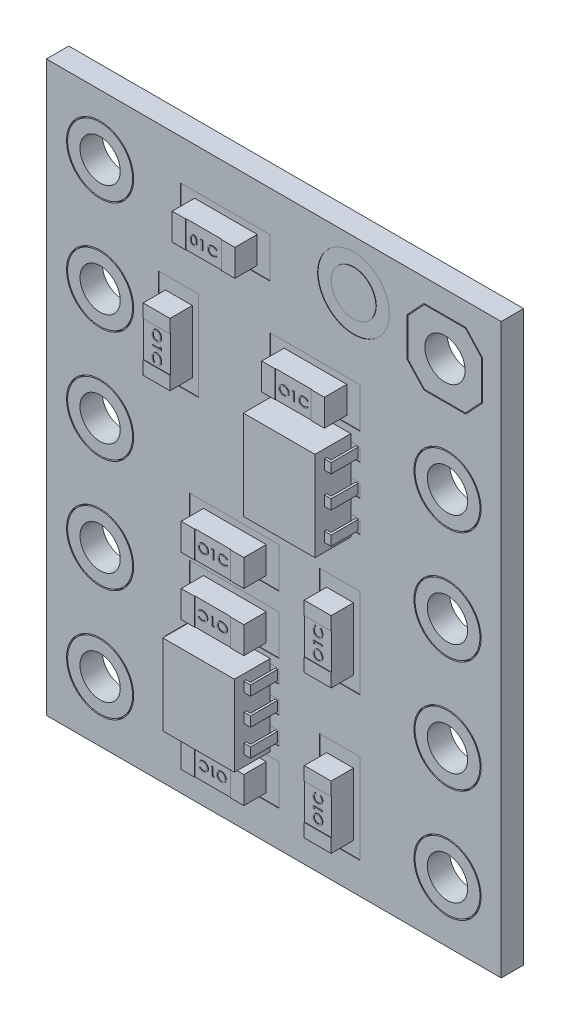
SolidWorks part; units mm, degrees
ref_plane "Alzado" through (0, 0, 0) normal (0, 0, 1) x (1, 0, 0)
ref_plane "Planta" through (0, 0, 0) normal (0, 1, 0) x (1, 0, 0)
ref_plane "Vista lateral" through (0, 0, 0) normal (1, 0, 0) x (0, 0, -1)
sketch "Croquis1" plane through (0, 0, 0) normal (0, 0, 1) x (1, 0, 0)
  line L0 (0, -0.275) -> (0, 0.275) construction
  line L1 (-5.08, 6.35) -> (5.08, 6.35)
  line L2 (-5.08, 6.35) -> (-5.08, -6.35)
  line L3 (-5.08, -6.35) -> (5.08, -6.35)
  line L4 (5.08, 6.35) -> (5.08, -6.35)
  line L6 (0.275, 0) -> (-0.275, 0) construction
  point P4 (-5.08, 0)
  point P5 (0, 6.35)
  dimension "D1" = 10.16
  dimension "D2" = 12.7
extrude "Saliente-Extruir2" add sketch "Croquis1" along normal blind 0.5
sketch "Croquis2" plane through (0, 0, 0.5) normal (0, 0, 1) x (1, 0, 0)
  line L0 (-3.88, 6.35) -> (-3.88, -6.35) construction
  line L1 (5.08, 6.35) -> (-5.08, 6.35) construction
  line L2 (-5.08, -6.35) -> (5.08, -6.35) construction
  line L3 (-5.08, 6.35) -> (-5.08, -6.35) construction
  line L4 (3.88, 6.35) -> (3.88, -6.35) construction
  line L5 (5.08, -6.35) -> (5.08, 6.35) construction
  line L6 (2.9786, 5.433) -> (2.9786, 4.567)
  line L7 (3.0025, 5.4294) -> (3.0025, 4.5706)
  line L8 (3.88, 5.8391) -> (3.355, 5.8391)
  line L9 (4.6663, 4.5655) -> (4.6663, 5.4331)
  line L10 (3.0025, 4.5706) -> (3.3638, 4.1809)
  line L11 (3.355, 4.1609) -> (4.2913, 4.1609)
  line L12 (3.88, 5.8191) -> (3.3638, 5.8191)
  line L13 (2.9786, 4.567) -> (3.355, 4.1609)
  line L14 (2.9786, 5.433) -> (3.355, 5.8391)
  line L15 (4.6663, 4.5655) -> (4.2913, 4.1609)
  line L16 (3.0019, 5.1573) -> (2.9033, 4.9865) [skipped]
  line L17 (4.2913, 4.1609) -> (4.2913, 5.9445) construction
  line L18 (3.3638, 4.1809) -> (3.88, 4.1809)
  line L19 (4.8787, 4.9484) -> (4.7801, 5.1192) [skipped]
  line L20 (4.3347, 4.1093) -> (4.5847, 4.5424) [skipped]
  line L21 (3.1533, 4.5805) -> (3.4033, 4.1474) [skipped]
  line L22 (4.6663, 5.4331) -> (4.2913, 5.8391)
  line L23 (3.88, 4.1809) -> (4.2826, 4.1809)
  line L24 (4.2913, 5.8391) -> (3.88, 5.8391)
  line L25 (3.88, 5.8191) -> (4.2825, 5.8191)
  line L26 (3.0025, 5.4294) -> (3.3638, 5.8191)
  line L27 (4.2825, 5.8191) -> (4.6425, 5.4294)
  line L28 (4.6425, 4.5693) -> (4.2826, 4.1809)
  line L29 (4.6425, 5.4294) -> (4.6425, 4.5693)
  line L31 (3.416, 5.7883) -> (3.3781, 5.7228) [skipped]
  line L32 (4.8041, 5.0837) -> (4.7663, 5.1492) [skipped]
  line L33 (4.4279, 4.2646) -> (4.4657, 4.3301) [skipped]
  line L34 (2.9653, 4.9923) -> (3.0031, 4.9268) [skipped]
  circle A0 centre (-3.88, 5) radius 0.75
  circle A1 centre (-3.88, 2.5) radius 0.75
  circle A2 centre (-3.88, 0) radius 0.75
  circle A3 centre (-3.88, -2.5) radius 0.75
  circle A4 centre (-3.88, -5) radius 0.75
  circle A5 centre (-3.88, 5) radius 0.725
  circle A6 centre (3.88, 2.5) radius 0.75
  circle A7 centre (3.88, 0) radius 0.75
  circle A8 centre (3.88, -2.5) radius 0.75
  circle A9 centre (3.88, -5) radius 0.75
  circle A10 centre (-3.88, 2.5) radius 0.725
  circle A11 centre (-3.88, 0) radius 0.725
  circle A12 centre (-3.88, -2.5) radius 0.725
  circle A13 centre (-3.88, -5) radius 0.725
  circle A14 centre (3.88, -5) radius 0.725
  circle A15 centre (3.88, -2.5) radius 0.725
  circle A16 centre (3.88, 0) radius 0.725
  circle A17 centre (3.88, 2.5) radius 0.725
  dimension "D2" = 1.5
  dimension "D3" = 1.5
  dimension "D4" = 1.5
  dimension "D5" = 1.5
  dimension "D6" = 1.5
  dimension "D13" = 1.45
  dimension "D14" = 1.5
  dimension "D15" = 1.5
  dimension "D16" = 1.5
  dimension "D17" = 1.5
  dimension "D20" = 1.45
  dimension "D21" = 1.45
  dimension "D22" = 1.45
  dimension "D23" = 1.45
  dimension "D24" = 1.45
  dimension "D25" = 1.45
  dimension "D26" = 1.45
  dimension "D27" = 1.45
  dimension "D1" = 1.2
  dimension "D7" = 1.35
  dimension "D8" = 2.5
  dimension "D9" = 2.5
  dimension "D10" = 2.5
  dimension "D11" = 2.5
  dimension "D12" = 1.2
  dimension "D18" = 2.5
  dimension "D19" = 2.5
  dimension "D28" = 0.02
  dimension "D29" = 0.02
  dimension "D30" = 0.02
  dimension "D31" = 0.02
  dimension "D32" = 0.02
  dimension "D35" = 0.02
extrude "Cortar-Extruir1" cut sketch "Croquis2" against normal blind 0.05
sketch "Croquis3" plane through (0, 0, 0.5) normal (0, 0, 1) x (1, 0, 0)
  line L0 (3.8231, 5.8191) -> (3.8232, 4.1809) construction
  line L1 (4.2825, 5.8191) -> (3.3638, 5.8191) construction
  line L2 (3.3638, 4.1809) -> (4.2826, 4.1809) construction
  line L3 (3.0025, 5) -> (4.6425, 4.9993) construction
  line L4 (3.0025, 5.4294) -> (3.0025, 4.5706) construction
  line L5 (4.6425, 4.5693) -> (4.6425, 5.4294) construction
  circle A0 centre (-3.88, -5) radius 0.45
  circle A1 centre (-3.88, -2.5) radius 0.45
  circle A2 centre (-3.88, 0) radius 0.45
  circle A3 centre (-3.88, 2.5) radius 0.45
  circle A4 centre (-3.88, 5) radius 0.45
  circle A5 centre (3.88, 2.5) radius 0.45
  circle A6 centre (3.88, 0) radius 0.45
  circle A7 centre (3.88, -2.5) radius 0.45
  circle A8 centre (3.88, -5) radius 0.45
  circle A9 centre (3.8232, 5) radius 0.45
  dimension "D1" = 0.9
  dimension "D2" = 0.9
  dimension "D3" = 0.9
  dimension "D4" = 0.9
  dimension "D5" = 0.9
  dimension "D6" = 0.9
  dimension "D7" = 0.9
  dimension "D8" = 0.9
  dimension "D9" = 0.9
  dimension "D10" = 0.9
extrude "Cortar-Extruir2" cut sketch "Croquis3" against normal blind 30.05
sketch "Croquis4" plane through (0, 0, 0.5) normal (0, 0, 1) x (1, 0, 0)
  line L0 (5.08, 6.35) -> (-5.08, 6.35) construction
  line L1 (5.08, -6.35) -> (5.08, 6.35) construction
  circle A0 centre (1.78, 5.25) radius 0.5
  circle A1 centre (1.78, 5.25) radius 0.8
  dimension "D3" = 1.6
  dimension "D4" = 1
  dimension "D1" = 1.1
  dimension "D2" = 3.3
extrude "Cortar-Extruir3" cut sketch "Croquis4" against normal blind 0.01
sketch "Croquis5" plane through (0, 0, 0.5) normal (0, 0, 1) x (1, 0, 0)
  line L0 (-5.08, 6.35) -> (-5.08, -6.35) construction
  line L1 (-2.08, 5.45) -> (-0.08, 5.45)
  line L2 (-2.08, 5.45) -> (-2.08, 4.55)
  line L3 (-2.08, 4.55) -> (-0.08, 4.55)
  line L4 (-0.08, 5.45) -> (-0.08, 4.55)
  line L5 (5.08, 6.35) -> (-5.08, 6.35) construction
  line L6 (-0.08, 2.05) -> (0.22, 2.05)
  line L7 (1.92, 3.55) -> (-0.08, 3.55)
  line L8 (1.92, 3.55) -> (1.92, 2.65)
  line L9 (1.92, 2.65) -> (-0.08, 2.65)
  line L10 (-0.08, 3.55) -> (-0.08, 2.65)
  line L11 (-2.58, 3.5) -> (-1.68, 3.5)
  line L12 (-2.58, 3.5) -> (-2.58, 1.5)
  line L13 (-2.58, 1.5) -> (-1.68, 1.5)
  line L14 (-1.68, 3.5) -> (-1.68, 1.5)
  line L15 (-0.08, 2.35) -> (0.22, 2.35)
  line L16 (-0.08, 2.35) -> (-0.08, 2.05)
  line L17 (-0.08, 0.65) -> (0.22, 0.65)
  line L18 (0.22, 2.35) -> (0.22, 2.05)
  line L19 (1.92, 2.35) -> (1.62, 2.35)
  line L20 (1.92, 2.35) -> (1.92, 2.05)
  line L21 (1.92, 0.65) -> (1.62, 0.65)
  line L22 (1.62, 2.35) -> (1.62, 2.05)
  line L23 (1.92, 0.95) -> (1.92, 0.65)
  line L24 (1.92, 1.65) -> (1.62, 1.65)
  line L25 (-0.08, 1.65) -> (-0.08, 1.35)
  line L26 (-0.08, 1.35) -> (0.22, 1.35)
  line L27 (-1.88, -3.15) -> (-1.58, -3.15)
  line L28 (1.92, 0.95) -> (1.62, 0.95)
  line L29 (-0.08, 0.95) -> (-0.08, 0.65)
  line L30 (0.22, 0.95) -> (0.22, 0.65)
  line L32 (0.22, 1.65) -> (0.22, 1.35)
  line L33 (1.62, 1.65) -> (1.62, 1.35)
  line L34 (1.92, 1.65) -> (1.92, 1.35)
  line L35 (1.62, 0.95) -> (1.62, 0.65)
  line L36 (1.62, 1.35) -> (1.92, 1.35)
  line L37 (0.22, 1.65) -> (-0.08, 1.65)
  line L38 (1.62, 2.05) -> (1.92, 2.05)
  line L39 (0.22, 0.95) -> (-0.08, 0.95)
  line L40 (-1.88, -3.45) -> (-1.88, -3.75)
  line L41 (-1.88, -0.45) -> (0.12, -0.45)
  line L42 (-1.88, -0.45) -> (-1.88, -1.35)
  line L43 (-1.88, -1.35) -> (0.12, -1.35)
  line L44 (0.12, -0.45) -> (0.12, -1.35)
  line L45 (-1.88, -1.75) -> (0.12, -1.75)
  line L46 (-1.88, -1.75) -> (-1.88, -2.65)
  line L47 (-1.88, -2.65) -> (0.12, -2.65)
  line L48 (0.12, -1.75) -> (0.12, -2.65)
  line L49 (-1.88, -4.65) -> (0.12, -4.65)
  line L50 (-1.88, -4.65) -> (-1.88, -5.55)
  line L51 (-1.88, -5.55) -> (0.12, -5.55)
  line L52 (0.12, -4.65) -> (0.12, -5.55)
  line L53 (-1.88, -2.85) -> (-1.58, -2.85)
  line L54 (-1.88, -2.85) -> (-1.88, -3.15)
  line L55 (-1.88, -4.35) -> (-1.58, -4.35)
  line L56 (-1.58, -2.85) -> (-1.58, -3.15)
  line L57 (0.12, -2.85) -> (-0.18, -2.85)
  line L58 (0.12, -2.85) -> (0.12, -3.15)
  line L59 (0.12, -4.35) -> (-0.18, -4.35)
  line L60 (-0.18, -2.85) -> (-0.18, -3.15)
  line L61 (-1.88, -3.75) -> (-1.58, -3.75)
  line L62 (0.12, -3.45) -> (-0.18, -3.45)
  line L64 (-1.88, -4.05) -> (-1.58, -4.05)
  line L65 (-1.88, -4.05) -> (-1.88, -4.35)
  line L66 (-1.58, -3.45) -> (-1.58, -3.75)
  line L67 (-0.18, -3.15) -> (0.12, -3.15)
  line L68 (-1.58, -3.45) -> (-1.88, -3.45)
  line L69 (-0.18, -3.45) -> (-0.18, -3.75)
  line L70 (0.12, -3.45) -> (0.12, -3.75)
  line L72 (-1.58, -4.05) -> (-1.58, -4.35)
  line L73 (-0.18, -3.75) -> (0.12, -3.75)
  line L74 (-0.18, -4.05) -> (0.12, -4.05)
  line L75 (-0.18, -4.05) -> (-0.18, -4.35)
  line L76 (0.12, -4.05) -> (0.12, -4.35)
  line L77 (1.92, -0.45) -> (1.02, -0.45)
  line L78 (1.92, -0.45) -> (1.92, -2.45)
  line L79 (1.92, -2.45) -> (1.02, -2.45)
  line L80 (1.02, -0.45) -> (1.02, -2.45)
  line L81 (1.02, -3.65) -> (1.92, -3.65)
  line L82 (1.02, -3.65) -> (1.02, -5.65)
  line L83 (1.02, -5.65) -> (1.92, -5.65)
  line L84 (1.92, -3.65) -> (1.92, -5.65)
  dimension "D1" = 0.9
  dimension "D2" = 2
  dimension "D3" = 3
  dimension "D4" = 1.8
  dimension "D5" = 2
  dimension "D6" = 2
  dimension "D7" = 1
  dimension "D8" = 0.9
  dimension "D9" = 0.9
  dimension "D10" = 2
  dimension "D11" = 2.5
  dimension "D12" = 0.3
  dimension "D13" = 0.3
  dimension "D14" = 1.7
  dimension "D15" = 1.7
  dimension "D16" = 0.3
  dimension "D17" = 0
  dimension "D18" = 0
  dimension "D19" = 0.3
  dimension "D20" = 0.3
  dimension "D21" = 0.3
  dimension "D22" = 0.3
  dimension "D23" = 0.4
  dimension "D24" = 0.9
  dimension "D25" = 0.9
  dimension "D26" = 0.9
  dimension "D27" = 1.1
  dimension "D28" = 0.4
  dimension "D29" = 2
  dimension "D30" = 0.3
  dimension "D31" = 0.3
  dimension "D32" = 0.2
  dimension "D33" = 0.3
  dimension "D34" = 0.3
  dimension "D35" = 0.3
  dimension "D36" = 0.3
  dimension "D37" = 0.3
  dimension "D38" = 0.3
  dimension "D39" = 0.3
  dimension "D40" = 2
  dimension "D41" = 3.2
  dimension "D42" = 2
  dimension "D43" = 0
  dimension "D44" = 0.9
  dimension "D45" = 0.9
  dimension "D46" = 0
  dimension "D47" = 2
  dimension "D48" = 1.2
extrude "Cortar-Extruir4" cut sketch "Croquis5" against normal blind 0.01
sketch "Croquis6" plane through (0, 0, 0.49) normal (0, 0, 1) x (1, 0, 0)
  line L0 (-0.08, 5.45) -> (-2.08, 5.45) construction
  line L1 (-1.78, 5.3) -> (-0.38, 5.3)
  line L2 (-1.78, 5.3) -> (-1.78, 4.7)
  line L3 (-1.78, 4.7) -> (-0.38, 4.7)
  line L4 (-0.38, 5.3) -> (-0.38, 4.7)
  line L5 (-2.08, 4.55) -> (-0.08, 4.55) construction
  line L6 (-2.08, 5.45) -> (-2.08, 4.55) construction
  line L7 (-0.08, 4.55) -> (-0.08, 5.45) construction
  line L8 (-1.68, 3.5) -> (-2.58, 3.5) construction
  line L9 (-2.43, 3.2) -> (-1.83, 3.2)
  line L10 (-2.43, 3.2) -> (-2.43, 1.8)
  line L11 (-2.43, 1.8) -> (-1.83, 1.8)
  line L12 (-1.83, 3.2) -> (-1.83, 1.8)
  line L13 (0.22, 3.4) -> (1.62, 3.4)
  line L14 (0.22, 3.4) -> (0.22, 2.8)
  line L15 (0.22, 2.8) -> (1.62, 2.8)
  line L16 (1.62, 3.4) -> (1.62, 2.8)
  line L17 (-1.58, -0.6) -> (-0.18, -0.6)
  line L18 (-1.58, -0.6) -> (-1.58, -1.2)
  line L19 (-1.58, -1.2) -> (-0.18, -1.2)
  line L20 (-0.18, -0.6) -> (-0.18, -1.2)
  line L21 (-1.58, -1.9) -> (-0.18, -1.9)
  line L22 (-1.58, -1.9) -> (-1.58, -2.5)
  line L23 (-1.58, -2.5) -> (-0.18, -2.5)
  line L24 (-0.18, -1.9) -> (-0.18, -2.5)
  line L25 (-1.58, -4.8) -> (-0.18, -4.8)
  line L26 (-1.58, -4.8) -> (-1.58, -5.4)
  line L27 (-1.58, -5.4) -> (-0.18, -5.4)
  line L28 (-0.18, -4.8) -> (-0.18, -5.4)
  line L29 (1.17, -0.75) -> (1.77, -0.75)
  line L30 (1.17, -0.75) -> (1.17, -2.15)
  line L31 (1.17, -2.15) -> (1.77, -2.15)
  line L32 (1.77, -0.75) -> (1.77, -2.15)
  line L33 (1.17, -3.95) -> (1.77, -3.95)
  line L34 (1.17, -3.95) -> (1.17, -5.35)
  line L35 (1.17, -5.35) -> (1.77, -5.35)
  line L36 (1.77, -3.95) -> (1.77, -5.35)
  line L37 (-2.58, 1.5) -> (-1.68, 1.5) construction
  line L38 (-2.58, 3.5) -> (-2.58, 1.5) construction
  line L39 (-1.68, 1.5) -> (-1.68, 3.5) construction
  line L40 (1.92, 3.55) -> (-0.08, 3.55) construction
  line L41 (-0.08, 2.65) -> (1.92, 2.65) construction
  line L42 (1.92, 2.65) -> (1.92, 3.55) construction
  line L43 (-0.08, 3.55) -> (-0.08, 2.65) construction
  line L44 (-1.88, -1.35) -> (0.12, -1.35) construction
  line L45 (0.12, -0.45) -> (-1.88, -0.45) construction
  line L46 (0.12, -1.35) -> (0.12, -0.45) construction
  line L47 (-1.88, -0.45) -> (-1.88, -1.35) construction
  line L48 (0.12, -1.75) -> (-1.88, -1.75) construction
  line L49 (-1.88, -2.65) -> (0.12, -2.65) construction
  line L50 (-1.88, -1.75) -> (-1.88, -2.65) construction
  line L51 (0.12, -2.65) -> (0.12, -1.75) construction
  line L52 (1.92, -0.45) -> (1.02, -0.45) construction
  line L53 (1.02, -2.45) -> (1.92, -2.45) construction
  line L54 (1.92, -2.45) -> (1.92, -0.45) construction
  line L55 (1.02, -0.45) -> (1.02, -2.45) construction
  line L56 (0.12, -4.65) -> (-1.88, -4.65) construction
  line L57 (-1.88, -5.55) -> (0.12, -5.55) construction
  line L58 (-1.88, -4.65) -> (-1.88, -5.55) construction
  line L59 (0.12, -5.55) -> (0.12, -4.65) construction
  line L60 (1.02, -5.65) -> (1.92, -5.65) construction
  line L61 (1.92, -3.65) -> (1.02, -3.65) construction
  line L62 (1.92, -5.65) -> (1.92, -3.65) construction
  line L63 (1.02, -3.65) -> (1.02, -5.65) construction
  dimension "D1" = 0.15
  dimension "D2" = 0.15
  dimension "D3" = 0.3
  dimension "D4" = 0.3
  dimension "D5" = 0.3
  dimension "D6" = 0.3
  dimension "D7" = 0.15
  dimension "D8" = 0.15
  dimension "D9" = 0.15
  dimension "D10" = 0.15
  dimension "D11" = 0.3
  dimension "D12" = 0.3
  dimension "D13" = 0.15
  dimension "D14" = 0.15
  dimension "D15" = 0.3
  dimension "D16" = 0.3
  dimension "D17" = 0.15
  dimension "D18" = 0.15
  dimension "D19" = 0.3
  dimension "D20" = 0.3
  dimension "D21" = 0.3
  dimension "D22" = 0.3
  dimension "D23" = 0.15
  dimension "D24" = 0.15
  dimension "D25" = 0.15
  dimension "D26" = 0.15
  dimension "D27" = 0.3
  dimension "D28" = 0.3
  dimension "D29" = 0.3
  dimension "D30" = 0.3
  dimension "D31" = 0.15
  dimension "D32" = 0.15
extrude "Saliente-Extruir3" add sketch "Croquis6" along normal blind 0.5
sketch "Croquis7" plane through (0, 0, 0.99) normal (0, 0, 1) x (1, 0, 0)
  line L0 (-0.38, 5.3) -> (-1.78, 5.3) construction
  line L1 (-1.48, 5.3) -> (-0.68, 5.3)
  line L2 (-1.48, 5.3) -> (-1.48, 4.7)
  line L3 (-1.48, 4.7) -> (-0.68, 4.7)
  line L4 (-0.68, 5.3) -> (-0.68, 4.7)
  line L5 (-1.78, 4.7) -> (-0.38, 4.7) construction
  line L6 (-2.43, 3.2) -> (-2.43, 1.8) construction
  line L7 (-2.43, 2.9) -> (-1.83, 2.9)
  line L8 (-2.43, 2.9) -> (-2.43, 2.1)
  line L9 (-2.43, 2.1) -> (-1.83, 2.1)
  line L10 (-1.83, 2.9) -> (-1.83, 2.1)
  line L11 (-1.83, 1.8) -> (-1.83, 3.2) construction
  line L12 (1.62, 3.4) -> (0.22, 3.4) construction
  line L13 (0.52, 3.4) -> (1.32, 3.4)
  line L14 (0.52, 3.4) -> (0.52, 2.8)
  line L15 (0.52, 2.8) -> (1.32, 2.8)
  line L16 (1.32, 3.4) -> (1.32, 2.8)
  line L17 (0.22, 2.8) -> (1.62, 2.8) construction
  line L18 (-0.18, -0.6) -> (-1.58, -0.6) construction
  line L19 (-1.28, -0.6) -> (-0.48, -0.6)
  line L20 (-1.28, -0.6) -> (-1.28, -1.2)
  line L21 (-1.28, -1.2) -> (-0.48, -1.2)
  line L22 (-0.48, -0.6) -> (-0.48, -1.2)
  line L23 (-1.58, -1.2) -> (-0.18, -1.2) construction
  line L24 (-0.18, -1.9) -> (-1.58, -1.9) construction
  line L25 (-1.28, -1.9) -> (-0.48, -1.9)
  line L26 (-1.28, -1.9) -> (-1.28, -2.5)
  line L27 (-1.28, -2.5) -> (-0.48, -2.5)
  line L28 (-0.48, -1.9) -> (-0.48, -2.5)
  line L29 (-1.58, -2.5) -> (-0.18, -2.5) construction
  line L30 (1.17, -0.75) -> (1.17, -2.15) construction
  line L31 (1.17, -1.05) -> (1.77, -1.05)
  line L32 (1.17, -1.05) -> (1.17, -1.85)
  line L33 (1.17, -1.85) -> (1.77, -1.85)
  line L34 (1.77, -1.05) -> (1.77, -1.85)
  line L35 (1.77, -2.15) -> (1.77, -0.75) construction
  line L36 (-0.18, -4.8) -> (-1.58, -4.8) construction
  line L37 (-1.28, -4.8) -> (-0.48, -4.8)
  line L38 (-1.28, -4.8) -> (-1.28, -5.4)
  line L39 (-1.28, -5.4) -> (-0.48, -5.4)
  line L40 (-0.48, -4.8) -> (-0.48, -5.4)
  line L41 (-1.58, -5.4) -> (-0.18, -5.4) construction
  line L42 (1.17, -3.95) -> (1.17, -5.35) construction
  line L43 (1.17, -4.25) -> (1.77, -4.25)
  line L44 (1.17, -4.25) -> (1.17, -5.05)
  line L45 (1.17, -5.05) -> (1.77, -5.05)
  line L46 (1.77, -4.25) -> (1.77, -5.05)
  line L47 (1.77, -5.35) -> (1.77, -3.95) construction
  line L48 (-1.78, 5.3) -> (-1.78, 4.7) construction
  line L49 (-0.38, 4.7) -> (-0.38, 5.3) construction
  line L50 (-1.83, 3.2) -> (-2.43, 3.2) construction
  line L51 (-2.43, 1.8) -> (-1.83, 1.8) construction
  line L52 (0.22, 3.4) -> (0.22, 2.8) construction
  line L53 (1.62, 2.8) -> (1.62, 3.4) construction
  line L54 (-1.58, -0.6) -> (-1.58, -1.2) construction
  line L55 (-0.18, -1.2) -> (-0.18, -0.6) construction
  line L56 (-1.58, -1.9) -> (-1.58, -2.5) construction
  line L57 (-0.18, -2.5) -> (-0.18, -1.9) construction
  line L58 (1.17, -2.15) -> (1.77, -2.15) construction
  line L59 (1.77, -0.75) -> (1.17, -0.75) construction
  line L60 (1.77, -3.95) -> (1.17, -3.95) construction
  line L61 (1.17, -5.35) -> (1.77, -5.35) construction
  line L62 (-1.58, -4.8) -> (-1.58, -5.4) construction
  line L63 (-0.18, -5.4) -> (-0.18, -4.8) construction
  dimension "D1" = 0.3
  dimension "D2" = 0.3
  dimension "D3" = 0.3
  dimension "D4" = 0.3
  dimension "D5" = 0.3
  dimension "D6" = 0.3
  dimension "D7" = 0.3
  dimension "D8" = 0.3
  dimension "D9" = 0.3
  dimension "D10" = 0.3
  dimension "D11" = 0.3
  dimension "D12" = 0.3
  dimension "D13" = 0.3
  dimension "D14" = 0.3
  dimension "D15" = 0.3
  dimension "D16" = 0.3
extrude "Cortar-Extruir5" cut sketch "Croquis7" against normal blind 0.01
sketch "Croquis8" plane through (0, 0, 0.5) normal (0, 0, 1) x (1, 0, 0)
  line L0 (1.92, 2.05) -> (1.92, 2.35) construction
  line L1 (0.12, 2.5) -> (1.72, 2.5)
  line L2 (0.12, 2.5) -> (0.12, 0.5)
  line L3 (0.12, 0.5) -> (1.72, 0.5)
  line L4 (1.72, 2.5) -> (1.72, 0.5)
  line L5 (-0.08, 2.35) -> (-0.08, 2.05) construction
  line L6 (-0.08, 2.65) -> (1.92, 2.65) construction
  line L7 (-1.88, -2.85) -> (-1.88, -3.15) construction
  line L8 (-1.68, -2.75) -> (-0.08, -2.75)
  line L9 (-1.68, -2.75) -> (-1.68, -4.55)
  line L10 (-1.68, -4.55) -> (-0.08, -4.55)
  line L11 (-0.08, -2.75) -> (-0.08, -4.55)
  line L14 (-1.88, -2.65) -> (0.12, -2.65) construction
  dimension "D1" = 0.2
  dimension "D2" = 0.2
  dimension "D3" = 0.15
  dimension "D4" = 2
  dimension "D5" = 0.2
  dimension "D6" = 1.6
  dimension "D7" = 0.1
  dimension "D8" = 1.8
extrude "Saliente-Extruir4" add sketch "Croquis8" along normal blind 0.8
sketch "Croquis9" plane through (0, 0, 0.49) normal (0, 0, 1) x (1, 0, 0)
  line L0 (0.12, 2.5) -> (0.12, 0.5) construction
  line L1 (-0.03, 2.31) -> (0.12, 2.31)
  line L2 (-0.03, 2.31) -> (-0.03, 2.09)
  line L3 (-0.03, 2.09) -> (0.12, 2.09)
  line L4 (0.12, 2.31) -> (0.12, 2.09)
  line L5 (1.72, 0.5) -> (1.72, 2.5) construction
  line L6 (-0.03, 1.61) -> (0.12, 1.61)
  line L7 (-0.03, 1.61) -> (-0.03, 1.39)
  line L8 (-0.03, 1.39) -> (0.12, 1.39)
  line L9 (0.12, 1.61) -> (0.12, 1.39)
  line L10 (1.72, 2.31) -> (1.87, 2.31)
  line L11 (1.72, 2.31) -> (1.72, 2.09)
  line L12 (1.72, 2.09) -> (1.87, 2.09)
  line L13 (1.87, 2.31) -> (1.87, 2.09)
  line L14 (0.12, 2.35) -> (-0.08, 2.35) construction
  line L15 (1.72, 1.61) -> (1.87, 1.61)
  line L16 (1.72, 1.61) -> (1.72, 1.39)
  line L17 (1.72, 1.39) -> (1.87, 1.39)
  line L18 (1.87, 1.61) -> (1.87, 1.39)
  line L19 (-0.03, 0.91) -> (0.12, 0.91)
  line L20 (-0.03, 0.91) -> (-0.03, 0.69)
  line L21 (-0.03, 0.69) -> (0.12, 0.69)
  line L22 (0.12, 0.91) -> (0.12, 0.69)
  line L23 (1.72, 0.91) -> (1.87, 0.91)
  line L24 (1.72, 0.91) -> (1.72, 0.69)
  line L25 (1.72, 0.69) -> (1.87, 0.69)
  line L26 (1.87, 0.91) -> (1.87, 0.69)
  line L27 (-0.08, 2.05) -> (0.12, 2.05) construction
  line L28 (-0.08, 2.35) -> (-0.08, 2.05) construction
  line L29 (1.92, 2.05) -> (1.92, 2.35) construction
  line L30 (1.92, 2.35) -> (1.72, 2.35) construction
  line L31 (1.62, 2.05) -> (1.92, 2.05) construction
  line L32 (1.92, 1.65) -> (1.72, 1.65) construction
  line L33 (1.62, 1.35) -> (1.92, 1.35) construction
  line L34 (1.92, 1.35) -> (1.92, 1.65) construction
  line L35 (0.12, 1.65) -> (-0.08, 1.65) construction
  line L36 (-0.08, 1.35) -> (0.22, 1.35) construction
  line L37 (-0.08, 1.65) -> (-0.08, 1.35) construction
  line L38 (-0.08, 0.95) -> (-0.08, 0.65) construction
  line L39 (0.22, 0.95) -> (-0.08, 0.95) construction
  line L40 (-0.08, 0.65) -> (0.12, 0.65) construction
  line L41 (1.92, 0.95) -> (1.72, 0.95) construction
  line L42 (1.62, 0.65) -> (1.92, 0.65) construction
  line L43 (1.92, 0.65) -> (1.92, 0.95) construction
  line L44 (-1.68, -2.75) -> (-1.68, -4.55) construction
  line L45 (-1.83, -2.89) -> (-1.68, -2.89)
  line L46 (-1.83, -2.89) -> (-1.83, -3.11)
  line L47 (-1.83, -3.11) -> (-1.68, -3.11)
  line L48 (-1.68, -2.89) -> (-1.68, -3.11)
  line L49 (-0.08, -4.55) -> (-0.08, -2.75) construction
  line L50 (-1.83, -3.49) -> (-1.68, -3.49)
  line L51 (-1.83, -3.49) -> (-1.83, -3.71)
  line L52 (-1.83, -3.71) -> (-1.68, -3.71)
  line L53 (-1.68, -3.49) -> (-1.68, -3.71)
  line L54 (-1.83, -4.09) -> (-1.68, -4.09)
  line L55 (-1.83, -4.09) -> (-1.83, -4.31)
  line L56 (-1.83, -4.31) -> (-1.68, -4.31)
  line L57 (-1.68, -4.09) -> (-1.68, -4.31)
  line L58 (-0.08, -4.09) -> (0.07, -4.09)
  line L59 (-0.08, -4.09) -> (-0.08, -4.31)
  line L60 (-0.08, -4.31) -> (0.07, -4.31)
  line L61 (0.07, -4.09) -> (0.07, -4.31)
  line L62 (-1.58, -2.85) -> (-1.88, -2.85) construction
  line L63 (-0.08, -3.49) -> (0.07, -3.49)
  line L64 (-0.08, -3.49) -> (-0.08, -3.71)
  line L65 (-0.08, -3.71) -> (0.07, -3.71)
  line L66 (0.07, -3.49) -> (0.07, -3.71)
  line L67 (-0.08, -2.89) -> (0.07, -2.89)
  line L68 (-0.08, -2.89) -> (-0.08, -3.11)
  line L69 (-0.08, -3.11) -> (0.07, -3.11)
  line L70 (0.07, -2.89) -> (0.07, -3.11)
  line L71 (-1.88, -3.15) -> (-1.58, -3.15) construction
  line L72 (-1.88, -2.85) -> (-1.88, -3.15) construction
  line L73 (0.12, -2.85) -> (-0.18, -2.85) construction
  line L74 (-0.18, -3.15) -> (0.12, -3.15) construction
  line L75 (0.12, -3.15) -> (0.12, -2.85) construction
  line L76 (-1.68, -3.45) -> (-1.88, -3.45) construction
  line L77 (-1.88, -3.75) -> (-1.68, -3.75) construction
  line L78 (0.12, -3.45) -> (-0.18, -3.45) construction
  line L79 (-0.08, -3.75) -> (0.12, -3.75) construction
  line L80 (-1.88, -3.45) -> (-1.88, -3.75) construction
  line L81 (0.12, -3.75) -> (0.12, -3.45) construction
  line L82 (-1.58, -4.05) -> (-1.88, -4.05) construction
  line L83 (-1.88, -4.35) -> (-1.58, -4.35) construction
  line L84 (-1.88, -4.05) -> (-1.88, -4.35) construction
  line L85 (0.12, -4.35) -> (0.12, -4.05) construction
  line L86 (0.12, -4.05) -> (-0.18, -4.05) construction
  line L87 (-0.08, -4.35) -> (0.12, -4.35) construction
  point P50 (-0.08, 1.5)
  dimension "D1" = 0.04
  dimension "D2" = 0.04
  dimension "D3" = 0.05
  dimension "D4" = 0.05
  dimension "D5" = 0.04
  dimension "D6" = 0.04
  dimension "D7" = 0.04
  dimension "D8" = 0.04
  dimension "D9" = 0.05
  dimension "D10" = 0.04
  dimension "D11" = 0.04
  dimension "D12" = 0.05
  dimension "D13" = 0.05
  dimension "D14" = 0.04
  dimension "D15" = 0.04
  dimension "D16" = 0.04
  dimension "D17" = 0.04
  dimension "D18" = 0.05
  dimension "D19" = 0.04
  dimension "D20" = 0.04
  dimension "D21" = 0.05
  dimension "D22" = 0.04
  dimension "D23" = 0.04
  dimension "D24" = 0.05
  dimension "D25" = 0.04
  dimension "D26" = 0.04
  dimension "D27" = 0.04
  dimension "D28" = 0.04
  dimension "D29" = 0.05
  dimension "D30" = 0.05
  dimension "D31" = 0.04
  dimension "D32" = 0.04
  dimension "D33" = 0.05
  dimension "D34" = 0.05
  dimension "D35" = 0.04
  dimension "D36" = 0.04
extrude "Saliente-Extruir5" add sketch "Croquis9" along normal blind 0.6
sketch "Croquis10" plane through (0, -4.31, 0) normal (0, -1, 0) x (1, 0, 0)
  line L8 (-0.08, 1.09) -> (-0.08, 0.5) construction
  line L9 (-0.08, 1.04) -> (0.02, 1.04)
  line L10 (-0.08, 1.04) -> (-0.08, 0.4971)
  line L11 (-0.08, 0.4971) -> (-0.08, 0.49)
  line L12 (0.02, 1.04) -> (0.02, 0.4971)
  line L13 (0.07, 1.09) -> (0.07, 0.49) construction
  line L14 (-0.08, 1.09) -> (0.07, 1.09) construction
  line L15 (-0.08, 0.49) -> (0.02, 0.49)
  line L16 (-0.08, 0.49) -> (0.07, 0.49) construction
  line L17 (0.02, 0.49) -> (0.02, 0.4971)
  dimension "D3" = 0.05
  dimension "D4" = 0.05
extrude "Cortar-Extruir6" cut sketch "Croquis10" against normal up to vertex (0.22 mm away) up to point (0.07, -4.09, 1.09)
sketch "Croquis11" plane through (0, -3.71, 0) normal (0, -1, 0) x (1, 0, 0)
  line L1 (-0.08, 1.04) -> (0.02, 1.04)
  line L2 (-0.08, 1.09) -> (-0.08, 0.5) construction
  line L3 (0.02, 1.04) -> (0.02, 0.49)
  line L4 (-0.08, 0.49) -> (0.07, 0.49) construction
  line L5 (0.02, 0.49) -> (-0.08, 0.49)
  line L6 (-0.08, 0.49) -> (-0.08, 1.04)
  line L7 (-0.08, 1.09) -> (0.07, 1.09) construction
  line L8 (0.07, 1.09) -> (0.07, 0.49) construction
  dimension "D1" = 0.05
  dimension "D2" = 0.05
extrude "Cortar-Extruir7" cut sketch "Croquis11" against normal up to vertex (0.22 mm away) up to point (0.07, -3.49, 1.09)
sketch "Croquis12" plane through (0, -3.11, 0) normal (0, -1, 0) x (1, 0, 0)
  line L0 (-0.08, 1.04) -> (0.02, 1.04)
  line L1 (-0.08, 1.09) -> (-0.08, 0.5) construction
  line L2 (0.02, 1.04) -> (0.02, 0.49)
  line L3 (-0.08, 0.49) -> (0.07, 0.49) construction
  line L4 (0.02, 0.49) -> (-0.08, 0.49)
  line L5 (-0.08, 0.49) -> (-0.08, 1.04)
  line L6 (-0.08, 1.09) -> (0.07, 1.09) construction
  line L7 (0.07, 1.09) -> (0.07, 0.49) construction
  dimension "D1" = 0.05
  dimension "D2" = 0.05
extrude "Cortar-Extruir8" cut sketch "Croquis12" against normal up to vertex (0.22 mm away) up to point (0.07, -2.89, 1.09)
sketch "Croquis13" plane through (0, 0.69, 0) normal (0, -1, 0) x (1, 0, 0)
  line L0 (1.72, 1.04) -> (1.82, 1.04)
  line L2 (1.72, 1.09) -> (1.72, 0.5) construction
  line L4 (1.82, 1.04) -> (1.82, 0.49)
  line L5 (1.72, 0.49) -> (1.87, 0.49) construction
  line L6 (1.82, 0.49) -> (1.72, 0.49)
  line L9 (1.72, 1.04) -> (1.72, 0.49)
  line L10 (1.87, 1.09) -> (1.87, 0.49) construction
  line L11 (1.72, 1.09) -> (1.87, 1.09) construction
  dimension "D1" = 0.05
  dimension "D2" = 0.05
extrude "Cortar-Extruir9" cut sketch "Croquis13" against normal up to vertex (0.22 mm away) up to point (1.87, 0.91, 1.09)
sketch "Croquis14" plane through (0, 1.39, 0) normal (0, -1, 0) x (1, 0, 0)
  line L0 (1.72, 1.04) -> (1.82, 1.04)
  line L1 (1.72, 1.09) -> (1.72, 0.5) construction
  line L2 (1.82, 1.04) -> (1.82, 0.49)
  line L3 (1.72, 0.49) -> (1.87, 0.49) construction
  line L4 (1.82, 0.49) -> (1.72, 0.49)
  line L5 (1.72, 0.49) -> (1.72, 1.04)
  line L6 (1.72, 1.09) -> (1.87, 1.09) construction
  line L7 (1.87, 1.09) -> (1.87, 0.49) construction
  dimension "D1" = 0.05
  dimension "D2" = 0.05
extrude "Cortar-Extruir10" cut sketch "Croquis14" against normal up to vertex (0.22 mm away) up to point (1.87, 1.61, 1.09)
sketch "Croquis15" plane through (0, 2.09, 0) normal (0, -1, 0) x (1, 0, 0)
  line L0 (1.72, 1.04) -> (1.82, 1.04)
  line L1 (1.72, 1.09) -> (1.72, 0.5) construction
  line L2 (1.82, 1.04) -> (1.82, 0.49)
  line L3 (1.72, 0.49) -> (1.87, 0.49) construction
  line L4 (1.82, 0.49) -> (1.72, 0.49)
  line L5 (1.72, 0.49) -> (1.72, 1.04)
  line L6 (1.72, 1.09) -> (1.87, 1.09) construction
  line L7 (1.87, 1.09) -> (1.87, 0.49) construction
  dimension "D1" = 0.05
  dimension "D2" = 0.05
extrude "Cortar-Extruir11" cut sketch "Croquis15" against normal up to vertex (0.22 mm away) up to point (1.87, 2.31, 1.09)
sketch "Croquis16" plane through (0, -4.31, 0) normal (0, -1, 0) x (1, 0, 0)
  line L0 (-1.68, 0.49) -> (-1.78, 0.49)
  line L1 (-1.83, 0.49) -> (-1.68, 0.49) construction
  line L2 (-1.78, 0.49) -> (-1.78, 1.04)
  line L3 (-1.78, 1.04) -> (-1.68, 1.04)
  line L4 (-1.68, 1.09) -> (-1.68, 0.5) construction
  line L5 (-1.68, 1.04) -> (-1.68, 0.49)
  line L6 (-1.83, 1.09) -> (-1.68, 1.09) construction
  line L7 (-1.83, 1.09) -> (-1.83, 0.49) construction
  dimension "D1" = 0.05
  dimension "D2" = 0.05
extrude "Cortar-Extruir12" cut sketch "Croquis16" against normal up to vertex (0.22 mm away) up to point (-1.83, -4.09, 1.09)
sketch "Croquis17" plane through (0, -3.71, 0) normal (0, -1, 0) x (1, 0, 0)
  line L0 (-1.68, 1.04) -> (-1.78, 1.04)
  line L1 (-1.68, 1.09) -> (-1.68, 0.5) construction
  line L2 (-1.78, 1.04) -> (-1.78, 0.49)
  line L3 (-1.83, 0.49) -> (-1.68, 0.49) construction
  line L4 (-1.78, 0.49) -> (-1.68, 0.49)
  line L5 (-1.68, 0.49) -> (-1.68, 1.04)
  line L6 (-1.83, 1.09) -> (-1.68, 1.09) construction
  line L7 (-1.83, 1.09) -> (-1.83, 0.49) construction
  dimension "D1" = 0.05
  dimension "D2" = 0.05
extrude "Cortar-Extruir13" cut sketch "Croquis17" against normal up to vertex (0.22 mm away) up to point (-1.83, -3.49, 1.09)
sketch "Croquis18" plane through (0, -3.11, 0) normal (0, -1, 0) x (1, 0, 0)
  line L0 (-1.68, 1.04) -> (-1.78, 1.04)
  line L1 (-1.68, 1.09) -> (-1.68, 0.5) construction
  line L2 (-1.78, 1.04) -> (-1.78, 0.49)
  line L3 (-1.83, 0.49) -> (-1.68, 0.49) construction
  line L4 (-1.78, 0.49) -> (-1.68, 0.49)
  line L5 (-1.68, 0.49) -> (-1.68, 1.04)
  line L6 (-1.83, 1.09) -> (-1.68, 1.09) construction
  line L7 (-1.83, 1.09) -> (-1.83, 0.49) construction
  dimension "D1" = 0.05
  dimension "D2" = 0.05
extrude "Cortar-Extruir15" cut sketch "Croquis18" against normal up to vertex (0.22 mm away) up to point (-1.83, -2.89, 1.09)
sketch "Croquis19" plane through (0, 0.69, 0) normal (0, -1, 0) x (1, 0, 0)
  line L0 (0.12, 1.04) -> (0.02, 1.04)
  line L1 (0.12, 1.09) -> (0.12, 0.5) construction
  line L2 (0.02, 1.04) -> (0.02, 0.49)
  line L3 (-0.03, 0.49) -> (0.12, 0.49) construction
  line L4 (0.02, 0.49) -> (0.12, 0.49)
  line L5 (0.12, 0.49) -> (0.12, 1.04)
  line L6 (-0.03, 1.09) -> (0.12, 1.09) construction
  line L7 (-0.03, 1.09) -> (-0.03, 0.49) construction
  dimension "D1" = 0.05
  dimension "D2" = 0.05
extrude "Cortar-Extruir16" cut sketch "Croquis19" against normal up to vertex (0.22 mm away) up to point (-0.03, 0.91, 1.09)
sketch "Croquis20" plane through (0, 1.39, 0) normal (0, -1, 0) x (1, 0, 0)
  line L0 (0.12, 1.04) -> (0.02, 1.04)
  line L1 (0.12, 1.09) -> (0.12, 0.5) construction
  line L2 (0.02, 1.04) -> (0.02, 0.49)
  line L3 (-0.03, 0.49) -> (0.12, 0.49) construction
  line L4 (0.02, 0.49) -> (0.12, 0.49)
  line L5 (0.12, 0.49) -> (0.12, 1.04)
  line L6 (-0.03, 1.09) -> (0.12, 1.09) construction
  line L7 (-0.03, 1.09) -> (-0.03, 0.49) construction
  dimension "D1" = 0.05
  dimension "D2" = 0.05
extrude "Cortar-Extruir17" cut sketch "Croquis20" against normal up to vertex (0.22 mm away) up to point (-0.03, 1.61, 1.09)
sketch "Croquis21" plane through (0, 2.09, 0) normal (0, -1, 0) x (1, 0, 0)
  line L0 (0.12, 1.04) -> (0.02, 1.04)
  line L1 (0.12, 1.09) -> (0.12, 0.5) construction
  line L2 (0.12, 1.04) -> (0.12, 0.49)
  line L4 (0.12, 0.49) -> (0.02, 0.49)
  line L6 (-0.03, 0.49) -> (0.12, 0.49) construction
  line L7 (-0.03, 1.09) -> (0.12, 1.09) construction
  line L9 (0.02, 0.49) -> (0.02, 1.04)
  dimension "D1" = 0.05
extrude "Cortar-Extruir18" cut sketch "Croquis21" against normal up to vertex (0.22 mm away) up to point (-0.03, 2.31, 1.09)
sketch "Croquis22" plane through (0, 0, 0.98) normal (0, 0, 1) x (1, 0, 0)
  line L0 (-1.48, 4.8682) -> (-0.68, 4.8682) construction
  line L1 (-1.48, 5.3) -> (-1.48, 4.7) construction
  line L2 (-0.68, 4.7) -> (-0.68, 5.3) construction
  text T0 "01C" font "Century Gothic" height 0.2
extrude "Saliente-Extruir6" add sketch "Croquis22" along normal blind 0.01
sketch "Croquis23" plane through (0, 0, 0.98) normal (0, 0, 1) x (1, 0, 0)
  line L0 (0.52, 2.9698) -> (1.32, 2.9698) construction
  line L1 (0.52, 3.4) -> (0.52, 2.8) construction
  line L2 (1.32, 2.8) -> (1.32, 3.4) construction
  line L3 (-1.28, -0.9943) -> (-0.48, -0.9943) construction
  line L4 (-1.28, -0.6) -> (-1.28, -1.2) construction
  line L5 (-0.48, -1.2) -> (-0.48, -0.6) construction
  text T0 "O1C" font "Century Gothic" height 0.2
  text T1 "O1C" font "Century Gothic" height 0.2
extrude "Saliente-Extruir7" add sketch "Croquis23" along normal blind 0.01
sketch "Croquis24" plane through (0, 0, 0.98) normal (0, 0, 1) x (1, 0, 0)
  line L0 (-0.48, -2.1) -> (-1.28, -2.1) construction
  line L1 (-0.48, -2.5) -> (-0.48, -1.9) construction
  line L2 (-1.28, -1.9) -> (-1.28, -2.5) construction
  line L3 (-0.18, -1.9) -> (-1.58, -1.9) construction
  line L4 (-0.48, -5) -> (-1.28, -5) construction
  line L5 (-0.48, -5.4) -> (-0.48, -4.8) construction
  line L6 (-1.28, -4.8) -> (-1.28, -5.4) construction
  line L7 (-0.48, -4.8) -> (-1.28, -4.8) construction
  text T0 "O1C" font "Century Gothic" height 0.2
  text T1 "O1C" font "Century Gothic" height 0.2
  dimension "D1" = 0.2
  dimension "D2" = 0.2
extrude "Saliente-Extruir8" add sketch "Croquis24" along normal blind 0.01
sketch "Croquis25" plane through (0, 0, 0.98) normal (0, 0, 1) x (1, 0, 0)
  line L0 (1.57, -1.05) -> (1.57, -1.85) construction
  line L1 (1.77, -1.05) -> (1.17, -1.05) construction
  line L2 (1.17, -1.85) -> (1.77, -1.85) construction
  line L3 (1.77, -1.85) -> (1.77, -1.05) construction
  line L4 (1.57, -4.25) -> (1.57, -5.05) construction
  line L5 (1.77, -4.25) -> (1.17, -4.25) construction
  line L6 (1.17, -5.05) -> (1.77, -5.05) construction
  text T0 "O1C" font "Century Gothic" height 0.2
  text T1 "O1C" font "Century Gothic" height 0.2
  dimension "D1" = 0.2
extrude "Saliente-Extruir9" add sketch "Croquis25" along normal blind 0.01
sketch "Croquis26" plane through (0, 0, 0.98) normal (0, 0, 1) x (1, 0, 0)
  line L0 (-2.23, 2.9) -> (-2.23, 2.1) construction
  line L1 (-1.83, 2.9) -> (-2.43, 2.9) construction
  line L2 (-2.43, 2.1) -> (-1.83, 2.1) construction
  line L3 (-2.43, 2.9) -> (-2.43, 2.1) construction
  text T0 "O1C" font "Century Gothic" height 0.2
  dimension "D1" = 0.2
extrude "Saliente-Extruir10" add sketch "Croquis26" along normal blind 0.01
